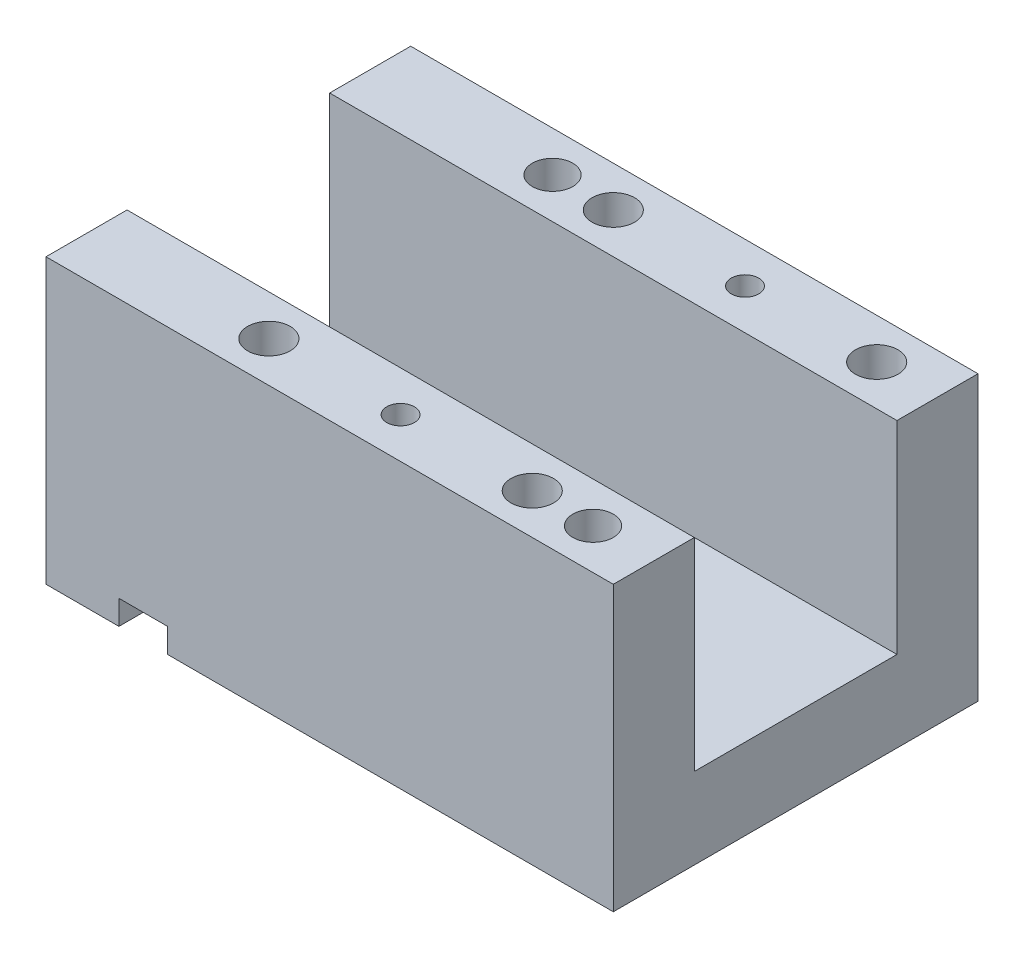
SolidWorks part; units mm, degrees
material "K110"
ref_plane "Front Plane" through (0, 0, 0) normal (0, 0, 1) x (1, 0, 0)
ref_plane "Top Plane" through (0, 0, 0) normal (0, 1, 0) x (1, 0, 0)
ref_plane "Right Plane" through (0, 0, 0) normal (1, 0, 0) x (0, 0, -1)
sketch "Sketch1" plane through (0, 0, 0) normal (0, 0, 1) x (1, 0, 0)
  line L1 (-70, -35) -> (70, -35)
  line L2 (-70, -35) -> (-70, 35)
  line L3 (-70, 35) -> (70, 35)
  line L4 (70, -35) -> (70, 35)
  line L5 (-70, -35) -> (70, 35) construction
  line L6 (-70, 35) -> (70, -35) construction
  point P0 (0, 0)
  dimension "D1" = 70
  dimension "D2" = 140
extrude "Boss-Extrude1" add sketch "Sketch1" along normal mid plane 90
sketch "Sketch2" plane through (0, 35, 0) normal (0, 1, 0) x (1, 0, 0)
  line L0 (-70, -45) -> (-70, 45) construction
  line L1 (-70, 25) -> (70, 25)
  line L2 (-70, 25) -> (-70, -25)
  line L3 (-70, -25) -> (70, -25)
  line L4 (70, 25) -> (70, -25)
  line L5 (70, -45) -> (70, 45) construction
  line L6 (-70, 0) -> (70, 0) construction
  dimension "D1" = 50
extrude "Cut-Extrude1" cut sketch "Sketch2" against normal blind 50 and the other way through all
hole_wizard "M10 Clearance Hole1" positions "Sketch10" profile "Sketch4" hole size "M10" standard "ISO" end condition through all
sketch "Sketch10" plane through (0, 35, 0) normal (0, 1, 0) x (1, 0, 0)
  line L0 (70, 35) -> (-70, 35) construction
  line L1 (70, 25) -> (70, 45) construction
  line L2 (-70, 25) -> (-70, 45) construction
  line L4 (70, -35) -> (-70, -35) construction
  line L5 (70, -45) -> (70, -25) construction
  line L6 (-70, -45) -> (-70, -25) construction
  point P0 (55, 35)
  point P2 (40, -35)
  point P4 (-25, -35)
  point P6 (-10, 35)
  dimension "D1" = 15
  dimension "D2" = 65
  dimension "D3" = 30
  dimension "D4" = 65
sketch "Sketch4" plane through (55, 35, -35) normal (1, 0, 0) x (0, 0, 1)
  line L0 (0, 0) -> (0, 70)
  line L1 (0, 70) -> (5.25, 70)
  line L2 (5.25, 70) -> (5.25, 0)
  line L5 (5.25, 0) -> (0, 0)
  line L11 (0, -6.35) -> (0, 107.95) construction
  dimension "Thru Hole Dia." = 10.5
  dimension "Thru Hole Depth" = 70
sketch "Sketch9" plane through (0, 0, 0) normal (0, 0, 1) x (1, 0, 0)
  line L0 (-70, -35) -> (70, -35) construction
  line L1 (-52, -35) -> (-40, -35)
  line L2 (-52, -35) -> (-52, -29)
  line L3 (-52, -29) -> (-40, -29)
  line L4 (-40, -35) -> (-40, -29)
  line L5 (-70, 35) -> (-70, -35) construction
  dimension "D1" = 6
  dimension "D2" = 12
  dimension "D3" = 30
extrude "Cut-Extrude2" cut sketch "Sketch9" against normal through all both and the other way through all
hole_wizard "Ø10.0mm Dowel Hole1" positions "Sketch13" profile "Sketch12" hole size "Ø10.0" standard "ISO" end condition through all
sketch "Sketch13" plane through (0, 35, 0) normal (0, 1, 0) x (1, 0, 0)
  line L0 (-70, 25) -> (-70, 45) construction
  line L1 (70, -45) -> (70, -25) construction
  line L2 (70, 25) -> (70, 45) construction
  point P0 (55, -35)
  point P2 (-25, 35)
  point P7 (-70, 35)
  point P12 (70, -35)
  dimension "D1" = 15
  dimension "D2" = 95
sketch "Sketch12" plane through (55, 35, 35) normal (1, 0, 0) x (0, 0, 1)
  line L0 (0, 0) -> (0, 70)
  line L1 (0, 70) -> (5, 70)
  line L2 (5, 70) -> (5, 0)
  line L5 (5, 0) -> (0, 0)
  line L11 (0, -6.35) -> (0, 107.95) construction
  dimension "Thru Hole Dia." = 10
  dimension "Thru Hole Depth" = 70
hole_wizard "M8 Tapped Hole1" positions "Sketch16" profile "Sketch15" tap size "M8" standard "ISO"
sketch "Sketch16" plane through (0, 35, 0) normal (0, 1, 0) x (1, 0, 0)
  line L0 (70, 25) -> (70, 45) construction
  line L1 (70, -45) -> (70, -25) construction
  point P0 (22.5, 35)
  point P2 (7.5, -35)
  point P7 (70, 35)
  point P10 (70, -35)
  dimension "D1" = 47.5
  dimension "D2" = 62.5
sketch "Sketch15" plane through (22.5, 35, -35) normal (1, 0, 0) x (0, 0, 1)
  line L0 (0, 0) -> (0, 19.75)
  line L1 (0, 19.75) -> (3.4, 17.7071)
  line L2 (3.4, 17.7071) -> (3.4, 0)
  line L5 (3.4, 0) -> (0, 0)
  line L10 (0, 19.75) -> (-3.4, 17.7071) construction
  line L11 (0, -6.35) -> (0, 107.95) construction
  dimension "Tap Drill Dia." = 6.8
  dimension "Tap Drill Depth" = 19.75
  dimension "Drill Angle" = 118
cosmetic thread "Hole Thread9"
cosmetic thread "Hole Thread10"
hole_wizard "M8 Tapped Hole2" positions "Sketch19" profile "Sketch18" tap size "M8" standard "ISO"
sketch "Sketch19" plane through (-70, 0, 0) normal (-1, 0, 0) x (0, 0, 1)
  line L0 (45, 35) -> (25, 35) construction
  line L1 (-25, 35) -> (-45, 35) construction
  line L2 (45, -35) -> (-45, -35) construction
  point P0 (-35, 23)
  point P2 (-35, -23)
  point P4 (35, 23)
  point P6 (35, -23)
  point P11 (35, 35)
  point P14 (-35, 35)
  dimension "D1" = 12
  dimension "D2" = 12
sketch "Sketch18" plane through (-70, 23, -35) normal (0, 1, 0) x (0, 0, 1)
  line L0 (0, 0) -> (0, 19.75)
  line L1 (0, 19.75) -> (3.4, 17.7071)
  line L2 (3.4, 17.7071) -> (3.4, 0)
  line L5 (3.4, 0) -> (0, 0)
  line L10 (0, 19.75) -> (-3.4, 17.7071) construction
  line L11 (0, -6.35) -> (0, 107.95) construction
  dimension "Tap Drill Dia." = 6.8
  dimension "Tap Drill Depth" = 19.75
  dimension "Drill Angle" = 118
cosmetic thread "Hole Thread11"
cosmetic thread "Hole Thread12"
cosmetic thread "Hole Thread13"
cosmetic thread "Hole Thread14"
